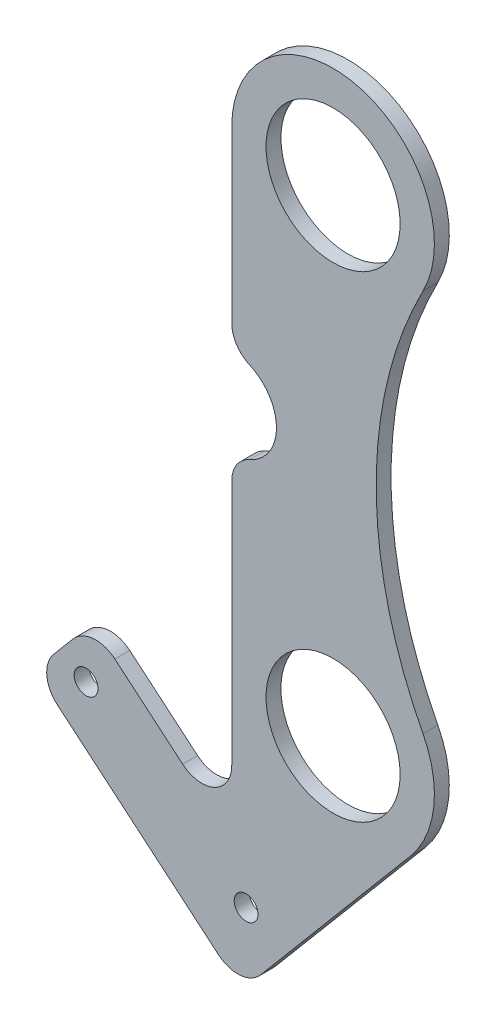
SolidWorks part; units mm, degrees
material "6061 Alloy"
ref_plane "Front Plane" through (0, 0, 0) normal (0, 0, 1) x (1, 0, 0)
ref_plane "Top Plane" through (0, 0, 0) normal (0, 1, 0) x (1, 0, 0)
ref_plane "Right Plane" through (0, 0, 0) normal (1, 0, 0) x (0, 0, -1)
sketch "Sketch1" plane through (0, 0, 0) normal (0, 0, 1) x (1, 0, 0)
  line L0 (0, 0) -> (0, -101.6) construction
  line L1 (21.59, -120.5575) -> (-21.59, -120.5575) construction
  line L2 (-8.89, 25.4) -> (8.89, 25.4)
  line L3 (-21.59, 12.7) -> (-21.59, -117.7751)
  line L5 (21.59, 12.7) -> (21.59, -117.7751)
  line L9 (-23.3829, -122.6853) -> (-33.2033, -134.3394)
  line L10 (-36.322, 25.4) -> (20.828, 25.4) construction
  line L11 (-36.322, 25.4) -> (-36.322, -203.2) construction
  line L12 (-36.322, -203.2) -> (20.828, -203.2) construction
  line L13 (20.828, 25.4) -> (20.828, -203.2) construction
  line L15 (-7.9527, -155.6168) -> (19.7971, -122.6853)
  line L16 (-32.4392, -143.2871) -> (-16.9004, -156.3809)
  circle A0 centre (0, 0) radius 38.1 construction
  circle A1 centre (0, -101.6) radius 38.1 construction
  circle A2 centre (0, 0) radius 14.2875
  circle A3 centre (0, -101.6) radius 14.2875
  arc A6 (8.89, 25.4) -> (21.59, 12.7) centre (8.89, 12.7) cw
  arc A7 (-8.89, 25.4) -> (-21.59, 12.7) centre (-8.89, 12.7) ccw
  circle A10 centre (-18.5321, -142.5501) radius 2.54
  arc A13 (-23.3829, -122.6853) -> (-21.59, -117.7751) centre (-29.21, -117.7751) ccw
  arc A14 (19.7971, -122.6853) -> (21.59, -117.7751) centre (13.97, -117.7751) ccw
  arc A15 (-16.9004, -156.3809) -> (-7.9527, -155.6168) centre (-12.8086, -151.525) ccw
  arc A16 (-33.2033, -134.3394) -> (-32.4392, -143.2871) centre (-28.3474, -138.4312) ccw
  point P13 (-192.705, 39.2708)
  point P20 (21.59, 25.4)
  point P23 (-21.59, 25.4)
  point P31 (-36.322, -138.0404)
  dimension "D2" = 76.2
  dimension "D3" = 76.2
  dimension "D4" = 28.575
  dimension "D5" = 28.575
  dimension "D10" = 228.6
  dimension "D11" = 36.322
  dimension "D13" = 5.08
  dimension "D19" = 6.35
  dimension "D20" = 7.62
  dimension "D21" = 12.7
  dimension "D1" = 101.6
  dimension "D6" = 43.18
  dimension "D7" = 21.59
  dimension "D8" = 25.4
  dimension "D9" = 57.15
  dimension "D12" = 25.4
  dimension "D14" = 33.02
  dimension "D15" = 16.51
  dimension "D16" = 21.59
  dimension "D17" = 9.525
  dimension "D18" = 18.9575
extrude "Boss-Extrude1" add sketch "Sketch1" along normal blind 3.175
sketch "Sketch2" plane through (0, 0, 0) normal (0, 0, 1) x (1, 0, 0)
  line L0 (-21.59, -41.275) -> (-21.59, -60.325)
  line L1 (0, 0) -> (0, -101.6) construction
  line L4 (21.59, -117.7751) -> (21.59, 12.7) construction
  line L5 (-21.59, -50.8) -> (97.79, -50.8) construction
  line L6 (-21.59, 12.7) -> (-21.59, -117.7751) construction
  line L7 (0, 0) -> (-39.9512, 0) construction
  line L9 (16.51, -115.5122) -> (-17.5013, -155.8745)
  line L10 (-32.4392, -143.2871) -> (-16.9004, -156.3809) construction
  line L11 (-7.9527, -155.6168) -> (19.7971, -122.6853) construction
  line L13 (27.94, -121.6567) -> (-7.6203, -163.8572)
  line L14 (-7.6203, -163.8572) -> (-17.5013, -155.8745)
  line L15 (27.94, -121.6567) -> (27.94, 0)
  line L16 (27.94, 0) -> (21.59, 0)
  arc A1 (19.1591, -91.6472) -> (19.1591, -9.9528) centre (97.79, -50.8) cw
  arc A2 (-21.59, -60.325) -> (-21.59, -41.275) centre (-21.59, -50.8) ccw
  arc A3 (21.59, 0) -> (19.1591, -9.9528) centre (0, 0) cw
  arc A4 (21.59, -101.6) -> (19.1591, -91.6472) centre (0, -101.6) ccw
  arc A5 (21.59, -101.6) -> (16.51, -115.5122) centre (0, -101.6) cw
  dimension "D2" = 12.7
  dimension "D3" = 50.8
  dimension "D4" = 6.35
  dimension "D1" = 76.2
  dimension "D5" = 19.05
extrude "Cut-Extrude1" cut sketch "Sketch2" along normal through all contours A1 A3 L16 L15 L13 L14 L9 A5 A4 | L0 A2
sketch "Sketch3" plane through (0, 0, 3.175) normal (0, 0, 1) x (1, 0, 0)
  line L0 (-27.3514, -127.3948) -> (-36.0255, -137.6886)
  line L3 (-27.3514, -127.3948) -> (-7.5576, -144.074)
  line L4 (-23.3829, -122.6853) -> (-33.2033, -134.3394) construction
  line L5 (16.51, -115.5122) -> (-17.5013, -155.8745) construction
  line L7 (-35.4064, -144.9387) -> (-24.4031, -154.2106)
  line L8 (-23.3829, -122.6853) -> (-33.2033, -134.3394) construction
  line L9 (-7.5576, -144.074) -> (-15.4554, -153.4465)
  line L10 (-32.4392, -143.2871) -> (-17.5013, -155.8745) construction
  circle A2 centre (-18.5321, -142.5501) radius 2.54
  circle A3 centre (-18.5321, -142.5501) radius 2.54 construction
  arc A5 (-36.0255, -137.6886) -> (-35.4064, -144.9387) centre (-32.0909, -141.0041) ccw
  arc A6 (-24.4031, -154.2106) -> (-15.4554, -153.4465) centre (-20.3113, -149.3547) ccw
  dimension "D2" = 6.35
  dimension "D3" = 5.1453
  dimension "D1" = 3.175
fillet "Fillet3" radius 6.35 2 edges at (-21.59, -41.275, 1.5875) (-21.59, -60.325, 1.5875)
extrude "Boss-Extrude3" add sketch "Sketch3" against normal blind 3.175
sketch "Sketch6" plane through (0, 0, 3.175) normal (0, 0, 1) x (1, 0, 0)
  line L0 (-35.4064, -144.9387) -> (-63.6204, -121.1641)
  line L1 (-63.6204, -121.1641) -> (-51.345, -106.5965)
  line L2 (-51.345, -106.5965) -> (-27.0656, -127.0555)
  line L4 (-35.4064, -144.9387) -> (-24.4031, -154.2106) construction
  line L5 (-23.3829, -122.6853) -> (-36.0255, -137.6886) construction
  line L6 (-35.4064, -144.9387) -> (-27.0656, -127.0555)
  circle A0 centre (-52.6268, -117.9721) radius 2.54
  point P11 (0, 0)
  point P12 (-34.1001, -146.0394)
  dimension "D4" = 5.08
  dimension "D1" = 31.75
  dimension "D2" = 9.525
  dimension "1" = 19.05
  dimension "D3" = 6.35
extrude "Boss-Extrude4" add sketch "Sketch6" against normal blind 3.175
fillet "Fillet2" radius 6.35 3 edges at (-63.6204, -121.1641, 1.5875) (-51.345, -106.5965, 1.5875) (-27.0656, -127.0555, 1.5875)
sketch "Sketch7" plane through (0, 0, 3.175) normal (0, 0, 1) x (1, 0, 0)
  line L0 (-21.59, 12.7) -> (-21.59, -36.2503) construction
  line L1 (21.59, 0) -> (21.59, 12.7) construction
  line L2 (-21.59, 0) -> (21.59, 0) construction
  line L3 (-21.59, 0) -> (-21.59, 31.75)
  line L4 (-21.59, 31.75) -> (21.59, 31.75)
  line L5 (21.59, 31.75) -> (21.59, 0)
  line L6 (8.89, 25.4) -> (-8.89, 25.4) construction
  arc A0 (-21.59, 0) -> (21.59, 0) centre (0, 0) cw
  dimension "D1" = 6.35
extrude "Cut-Extrude2" cut sketch "Sketch7" against normal through all
sketch "Sketch10" plane through (0, 0, 3.175) normal (0, 0, 1) x (1, 0, 0)
  line L0 (16.51, -115.5122) -> (-17.5013, -155.8745) construction
  line L1 (-18.1519, -155.3263) -> (-17.3615, -157.512)
  line L2 (-17.3615, -157.512) -> (-14.3757, -156.4323)
  line L3 (-14.3757, -156.4323) -> (-15.4554, -153.4465)
  line L5 (-18.1519, -155.3263) -> (-17.5013, -155.8745) construction
  circle A0 centre (-20.3113, -149.3547) radius 6.35 construction
  arc A1 (-24.4031, -154.2106) -> (-18.1519, -155.3263) centre (-20.3113, -149.3547) ccw construction
  arc A2 (-18.1519, -155.3263) -> (-15.4554, -153.4465) centre (-20.3113, -149.3547) ccw
  point P10 (-14.3271, -156.4143)
  dimension "D1" = 3.175
  dimension "D2" = 30
extrude "Cut-Extrude3" cut sketch "Sketch10" against normal through all
